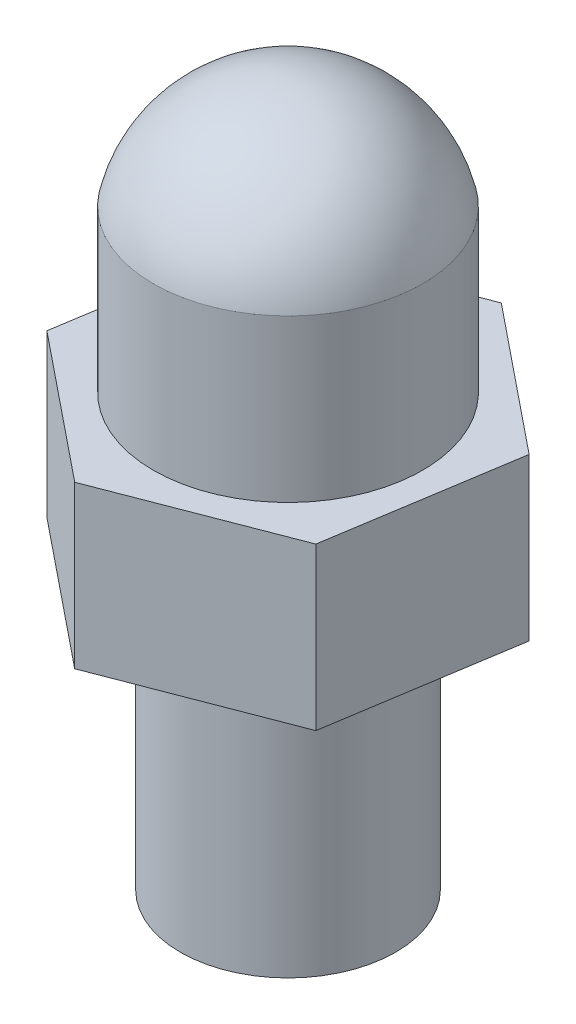
SolidWorks part; units mm, degrees
ref_plane "Ön Düzlem" through (0, 0, 0) normal (0, 0, 1) x (1, 0, 0)
ref_plane "Üst Düzlem" through (0, 0, 0) normal (0, 1, 0) x (1, 0, 0)
ref_plane "Sağ Düzlem" through (0, 0, 0) normal (1, 0, 0) x (0, 0, -1)
sketch "Çizim1" plane through (0, 0, 0) normal (0, 1, 0) x (1, 0, 0)
  circle A0 centre (0, 0) radius 2
  dimension "D1" = 4
extrude "Yükseklik-Ekstrüzyon1" add sketch "Çizim1" along normal blind 5
sketch "Çizim2" plane through (0, 5, 0) normal (0, 1, 0) x (1, 0, 0)
  line L1 (2.6942, -2.1775) -> (3.2328, 1.2445)
  line L2 (3.2328, 1.2445) -> (0.5387, 3.422)
  line L3 (0.5387, 3.422) -> (-2.6942, 2.1775)
  line L4 (-2.6942, 2.1775) -> (-3.2328, -1.2445)
  line L5 (-3.2328, -1.2445) -> (-0.5387, -3.422)
  line L6 (-0.5387, -3.422) -> (2.6942, -2.1775)
  circle A0 centre (0, 0) radius 3 construction
  dimension "D1" = 6
extrude "Yükseklik-Ekstrüzyon2" add sketch "Çizim2" along normal blind 3
sketch "Çizim3" plane through (0, 8, 0) normal (0, 1, 0) x (1, 0, 0)
  circle A0 centre (0, 0) radius 2.5
  dimension "D1" = 5
extrude "Yükseklik-Ekstrüzyon3" add sketch "Çizim3" along normal blind 3
dome "Kubbe1" faces to dome 1 distance 2 reverse direction no elliptical dome no face at (0, 11, 2.5) parameters "D1"=2
